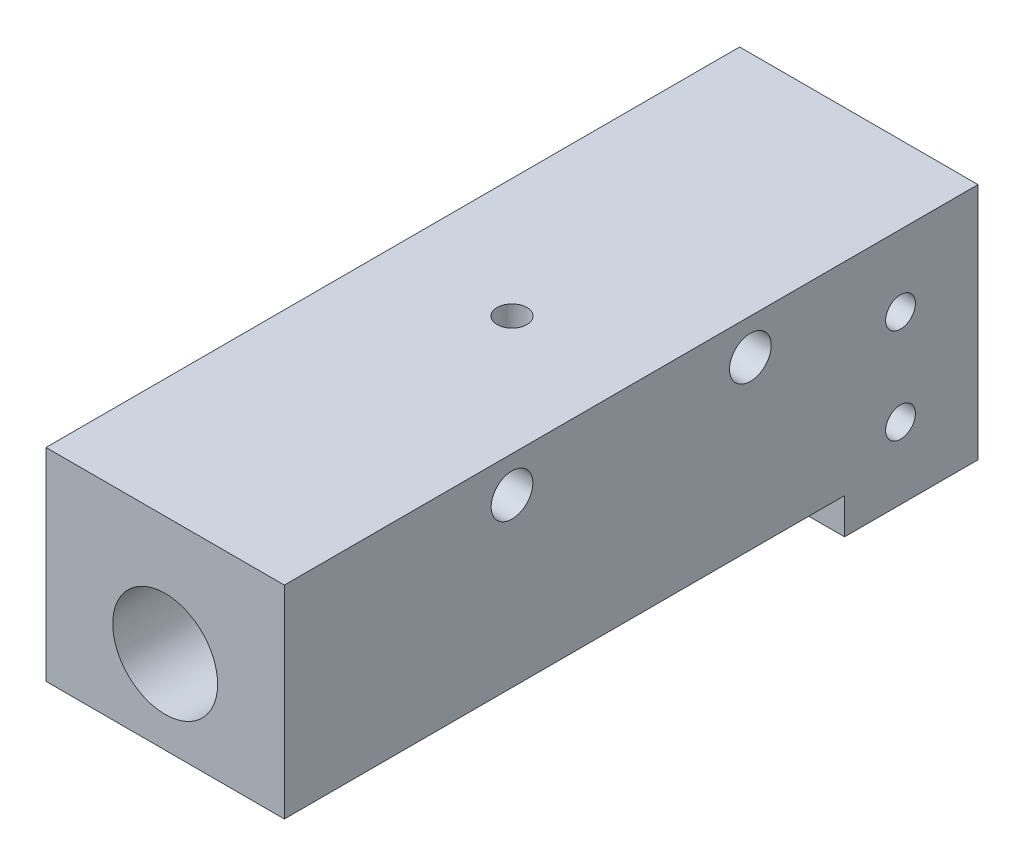
SolidWorks part; units mm, degrees
material "6063-T5"
ref_plane "Piano frontale" through (0, 0, 0) normal (0, 0, 1) x (1, 0, 0)
ref_plane "Piano superiore" through (0, 0, 0) normal (0, 1, 0) x (1, 0, 0)
ref_plane "Piano destro" through (0, 0, 0) normal (1, 0, 0) x (0, 0, -1)
sketch "Schizzo1" plane through (0, 0, 0) normal (0, 0, 1) x (1, 0, 0)
  line L1 (10, -10) -> (-10, -10)
  line L2 (10, -10) -> (10, 10)
  line L3 (10, 10) -> (-10, 10)
  line L4 (-10, -10) -> (-10, 10)
  line L5 (10, -10) -> (-10, 10) construction
  line L6 (10, 10) -> (-10, -10) construction
  point P0 (0, 0)
  dimension "D1" = 20
  dimension "D2" = 20
extrude "Estrusione-Estrusione1" add sketch "Schizzo1" against normal blind 58.2
sketch "Schizzo2" plane through (0, 0, -58.2) normal (0, 0, -1) x (-1, 0, 0)
  circle A0 centre (0, 0) radius 3
  dimension "D1" = 6
extrude "Taglio-Estrusione1" cut sketch "Schizzo2" against normal through all
sketch "Schizzo3" plane through (0, 0, -58.2) normal (0, 0, -1) x (-1, 0, 0)
  circle A0 centre (0, 0) radius 6
  dimension "D1" = 12
extrude "Taglio-Estrusione2" cut sketch "Schizzo3" against normal blind 13
sketch "Schizzo4" plane through (10, 0, 0) normal (1, 0, 0) x (0, 0, -1)
  line L0 (0, 7) -> (58.2, 7) construction
  line L1 (0, -10) -> (0, 10) construction
  line L2 (58.2, -10) -> (58.2, 10) construction
  line L3 (58.2, 10) -> (0, 10) construction
  line L4 (29.1, 10) -> (29.1, -10) construction
  line L5 (58.2, -10) -> (0, -10) construction
  circle A0 centre (19.1, 7) radius 1.75
  circle A1 centre (39.1, 7) radius 1.75
  dimension "D2" = 3.5
  dimension "D1" = 3
  dimension "D3" = 10
extrude "Taglio-Estrusione3" cut sketch "Schizzo4" against normal through all
hole_wizard "Foro filettato G1/8-1" positions "Schizzo8" profile "Schizzo7" tap size "G1/8" standard "BSI"
sketch "Schizzo8" plane through (0, 0, 0) normal (0, 0, 1) x (1, 0, 0)
  point P0 (0, 0)
sketch "Schizzo7" plane through (0, 0, 0) normal (1, 0, 0) x (0, -1, 0)
  line L0 (0, 0) -> (0, 12.6438)
  line L1 (0, 12.6438) -> (4.4, 10)
  line L2 (4.4, 10) -> (4.4, 0)
  line L5 (4.4, 0) -> (0, 0)
  line L10 (0, 12.6438) -> (-4.4, 10) construction
  line L11 (0, -6.35) -> (0, 107.95) construction
  dimension "Tap Drill Dia." = 8.8
  dimension "Tap Drill Depth" = 10
  dimension "Drill Angle" = 118
sketch "Schizzo10" plane through (10, 0, 0) normal (1, 0, 0) x (0, 0, -1)
  line L0 (0, -7) -> (47, -7)
  line L1 (0, -10) -> (0, 10) construction
  line L2 (47, -7) -> (47, -10)
  line L3 (58.2, -10) -> (0, -10) construction
  dimension "D1" = 47
  dimension "D2" = 3
extrude "Taglio-Estrusione5" cut sketch "Schizzo10" against normal through all and the other way through all flip side to cut
sketch "Schizzo11" plane through (0, 10, 0) normal (0, 1, 0) x (1, 0, 0)
  line L0 (0, 58.2) -> (0, 0) construction
  line L1 (10, 58.2) -> (-10, 58.2) construction
  line L2 (10, 29.1) -> (-10, 29.1) construction
  line L3 (10, 58.2) -> (10, 0) construction
  point P10 (0, 29.1)
  point P11 (0, 29.1)
  point P12 (0, 29.1)
hole_wizard "Foro filettato M3-1" positions "Schizzo3D1" profile "Schizzo12" tap size "M3" standard "DIN"
sketch3d "Schizzo3D1"
  point P0 (0, 10, -29.1)
sketch "Schizzo12" plane through (0, 10, -29.1) normal (1, 0, 0) x (0, 0, 1)
  line L0 (0, 0) -> (0, 5.7511)
  line L1 (0, 5.7511) -> (1.25, 5)
  line L2 (1.25, 5) -> (1.25, 0)
  line L5 (1.25, 0) -> (0, 0)
  line L10 (0, 5.7511) -> (-1.25, 5) construction
  line L11 (0, -6.35) -> (0, 107.95) construction
  dimension "Tap Drill Dia." = 2.5
  dimension "Tap Drill Depth" = 5
  dimension "Drill Angle" = 118
sketch "Schizzo13" plane through (10, 0, 0) normal (1, 0, 0) x (0, 0, -1)
  line L0 (45.2, 0) -> (58.2, 0) construction
  line L1 (45.2, -6) -> (45.2, 6) construction
  line L2 (58.2, -10) -> (58.2, 10) construction
  line L3 (51.7, 6) -> (51.7, -6) construction
  line L4 (58.2, 6) -> (45.2, 6) construction
  line L5 (45.2, -6) -> (58.2, -6) construction
  point P12 (51.7, 4)
  point P13 (51.7, -4)
  dimension "D1" = 4
hole_wizard "Foro filettato M3-2" positions "Schizzo3D2" profile "Schizzo14" tap size "M3" standard "DIN"
sketch3d "Schizzo3D2"
  point P0 (10, 4, -51.7)
  point P3 (10, -4, -51.7)
sketch "Schizzo14" plane through (10, 4, -51.7) normal (0, 1, 0) x (0, 0, -1)
  line L0 (0, 0) -> (0, 7.2511)
  line L1 (0, 7.2511) -> (1.25, 6.5)
  line L2 (1.25, 6.5) -> (1.25, 0)
  line L5 (1.25, 0) -> (0, 0)
  line L10 (0, 7.2511) -> (-1.25, 6.5) construction
  line L11 (0, -6.35) -> (0, 107.95) construction
  dimension "Tap Drill Dia." = 2.5
  dimension "Tap Drill Depth" = 6.5
  dimension "Drill Angle" = 118
